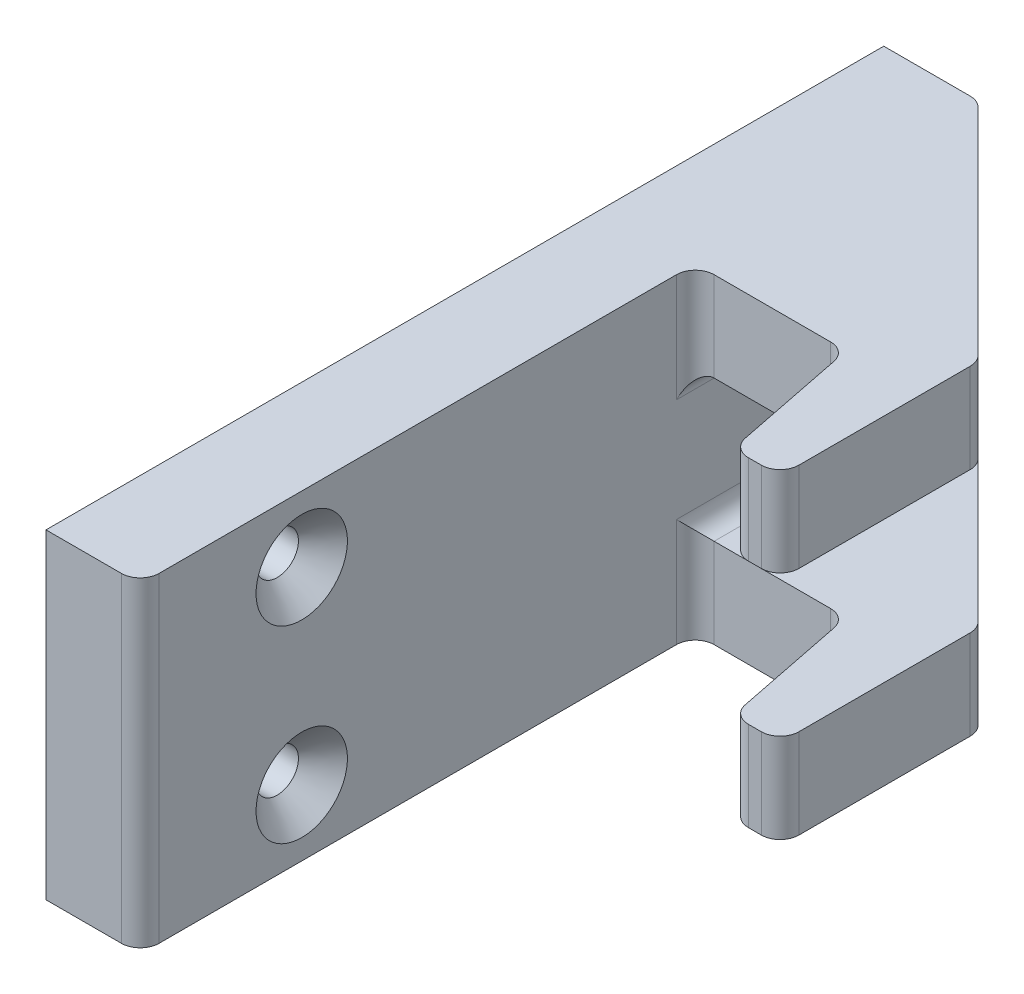
SolidWorks part; units mm, degrees
ref_plane "Front Plane" through (0, 0, 0) normal (1, 0, 0) x (0, 1, 0)
ref_plane "Top Plane" through (0, 0, 0) normal (0, 0, 1) x (0, 1, 0)
ref_plane "Right Plane" through (0, 0, 0) normal (0, 1, 0) x (-1, 0, 0)
sketch "Sketch1" plane through (0, 0, 0) normal (0, 1, 0) x (-1, 0, 0)
  line L0 (-2, 0) -> (-14.3604, 0)
  line L1 (-16, 0) -> (-16, 15) construction
  line L2 (-16, 15) -> (-19, 15) construction
  line L3 (-18.6784, 13.3922) -> (-16.3216, 1.6078)
  line L4 (-20.6396, 15) -> (-22, 15)
  line L5 (-24, 13) -> (-24, 0)
  line L6 (-24, 0) -> (-24, -5.1716)
  line L7 (-23.4142, -6.5858) -> (-0.5858, -29.4142)
  line L8 (0.8284, -30) -> (10, -30)
  line L9 (0, 2) -> (0, 56.9)
  line L10 (2, 58.9) -> (10, 58.9)
  line L11 (10, 58.9) -> (10, -30)
  arc A0 (0.8284, -30) -> (-0.5858, -29.4142) centre (0.8284, -28) cw
  arc A1 (-23.4142, -6.5858) -> (-24, -5.1716) centre (-22, -5.1716) cw
  arc A2 (-24, 13) -> (-22, 15) centre (-22, 13) cw
  arc A3 (-18.6784, 13.3922) -> (-20.6396, 15) centre (-20.6396, 13) ccw
  arc A4 (-16.3216, 1.6078) -> (-14.3604, 0) centre (-14.3604, 2) ccw
  arc A5 (0, 2) -> (-2, 0) centre (-2, 2) cw
  arc A6 (2, 58.9) -> (0, 56.9) centre (2, 56.9) ccw
  point P16 (-24, -6)
  point P27 (0, 0)
  dimension "D2" = 2
  dimension "D3" = 2
  dimension "D1" = 6
extrude "Boss-Extrude1" add sketch "Sketch1" along normal blind 34
sketch "Sketch2" plane through (0, 0, 0) normal (0, 0, 1) x (1, 0, 0)
  line L0 (0, 9.5) -> (0, 24.5)
  line L2 (0, 24.5) -> (27.2459, 24.5)
  line L3 (27.2459, 24.5) -> (27.2459, 9.5)
  line L4 (27.2459, 9.5) -> (0, 9.5)
  point P4 (0, 17)
  dimension "D1" = 15
extrude "Cut-Extrude1" cut sketch "Sketch2" against normal blind 34 and the other way blind 34
fillet "Fillet1" radius 2 2 edges at (0, 24.5, -13.9102) (0, 9.5, -13.9102)
sketch "Sketch3" plane through (0, 0, 0) normal (1, 0, 0) x (0, 1, 0)
  line L0 (7, 41.7635) -> (27, 41.7635) construction
  circle A0 centre (17, -13.9102) radius 2.25
  circle A1 centre (7, 41.7635) radius 2.25
  circle A2 centre (27, 41.7635) radius 2.25
  point P5 (17, 41.7635)
  dimension "D1" = 20
extrude "Cut-Extrude2" cut sketch "Sketch3" against normal blind 34
chamfer "Chamfer1" distance 2.6 angle 45 3 edges at (0, 17, -16.1602) (0, 27, 39.5135) (0, 7, 39.5135)
sketch "Sketch8" plane through (-10, 0, 0) normal (-1, 0, 0) x (0, -1, 0)
  line L0 (-24.649, 31.9209) -> (-24.649, -7.0193) construction
  text T0 "https://github.com/\r\nmehammer986/SSMR"
extrude "Cut-Extrude3" cut sketch "Sketch8" against normal blind 1
